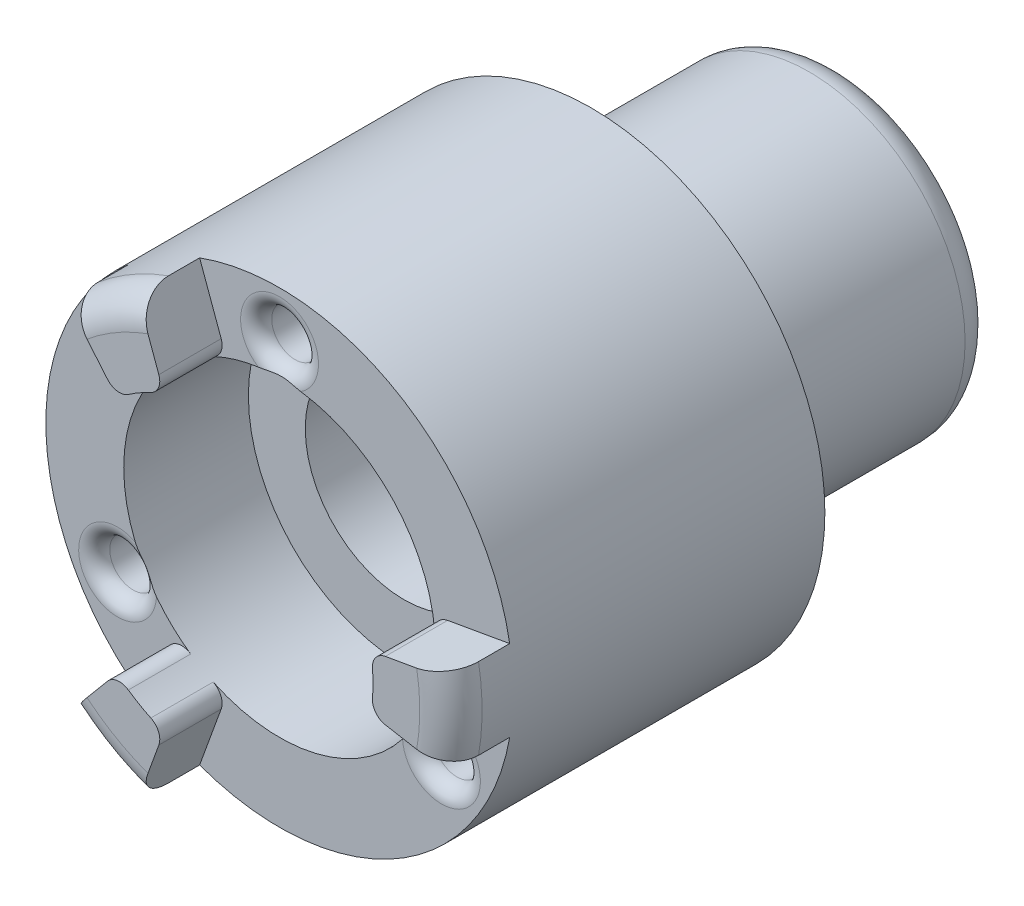
SolidWorks part; units mm, degrees
material "PET"
ref_plane "Front Plane" through (0, 0, 0) normal (0, 0, 1) x (1, 0, 0)
ref_plane "Top Plane" through (0, 0, 0) normal (0, 1, 0) x (1, 0, 0)
ref_plane "Right Plane" through (0, 0, 0) normal (1, 0, 0) x (0, 0, -1)
sketch "Sketch1" plane through (0, 0, 0) normal (0, 0, 1) x (1, 0, 0)
  line L0 (0, 0) -> (0, 2.5) construction
  line L1 (0, 2.625) -> (0, 3) construction
  line L2 (0, 2.625) -> (0, 2.5) construction
  circle A0 centre (0, 0) radius 2.5
  circle A1 centre (0, 0) radius 3.75
  circle A2 centre (0, 3) radius 0.375
  circle A3 centre (2.5981, -1.5) radius 0.375
  circle A4 centre (-2.5981, -1.5) radius 0.375
  point P15 (0, 0)
  dimension "D1" = 5
  dimension "D2" = 0.75
  dimension "D4" = 7.5
  dimension "D3" = 3
  dimension "D5" = 3
extrude "Boss-Extrude1" add sketch "Sketch1" along normal blind 5
sketch "Sketch2" plane through (0, 0, 5) normal (0, 0, 1) x (1, 0, 0)
  line L0 (-1.607, -1.9151) -> (-2.4105, -2.8727)
  line L1 (0, 0) -> (-2.061, -3.5698) construction
  line L2 (-0.8551, -2.3492) -> (-1.2826, -3.5238)
  line L3 (-0.8551, 2.3492) -> (-1.2826, 3.5238)
  line L4 (-1.607, 1.9151) -> (-2.4105, 2.8727)
  line L5 (2.462, -0.4341) -> (3.693, -0.6512)
  line L6 (2.462, 0.4341) -> (3.693, 0.6512)
  line L7 (0, 0) -> (0, -5.9665) construction
  circle A0 centre (0, 0) radius 3.75 construction
  arc A1 (-2.4105, -2.8727) -> (-1.2826, -3.5238) centre (0, 0) ccw
  arc A3 (-1.607, -1.9151) -> (-0.8551, -2.3492) centre (0, 0) ccw
  circle A4 centre (0, 0) radius 2.5 construction
  arc A5 (-1.2826, 3.5238) -> (-2.4105, 2.8727) centre (0, 0) ccw
  arc A6 (-0.8551, 2.3492) -> (-1.607, 1.9151) centre (0, 0) ccw
  arc A7 (3.693, -0.6512) -> (3.693, 0.6512) centre (0, 0) ccw
  arc A8 (2.462, -0.4341) -> (2.462, 0.4341) centre (0, 0) ccw
  point P20 (0, 0)
  dimension "D1" = 10
  dimension "D3" = 30
  dimension "D2" = 3
extrude "Boss-Extrude2" add sketch "Sketch2" along normal blind 1 and the other way blind 4
fillet "Fillet1" radius 0.5 3 edges at (-1.875, 3.2476, 6) (-1.875, -3.2476, 6) (3.75, 0, 6)
fillet "Fillet2" radius 0.25 6 edges at (0.375, 3, 0) (0.375, 3, 5) (2.9731, -1.5, 0) (2.9731, -1.5, 5) (-2.2231, -1.5, 0) (-2.2231, -1.5, 5)
fillet "Fillet3" radius 0.25 6 edges at (-1.607, 1.9151, 5.5) (2.462, -0.4341, 5.5) (-0.8551, -2.3492, 5.5) (-1.607, -1.9151, 5.5) (-0.8551, 2.3492, 5.5) (2.462, 0.4341, 5.5)
sketch "Sketch3" plane through (0, 0, 0) normal (0, 0, 1) x (1, 0, 0)
  circle A0 centre (0, 0) radius 2.5
  arc A1 (-1.0651, -2.2618) -> (1.974, -1.534) centre (0, 0) ccw construction
  circle A2 centre (0, 0) radius 1.5875
  dimension "D1" = 3.175
extrude "Boss-Extrude3" add sketch "Sketch3" along normal blind 3 and the other way blind 4
fillet "Fillet4" radius 0.5 1 edges at (2.5, 0, -4)
